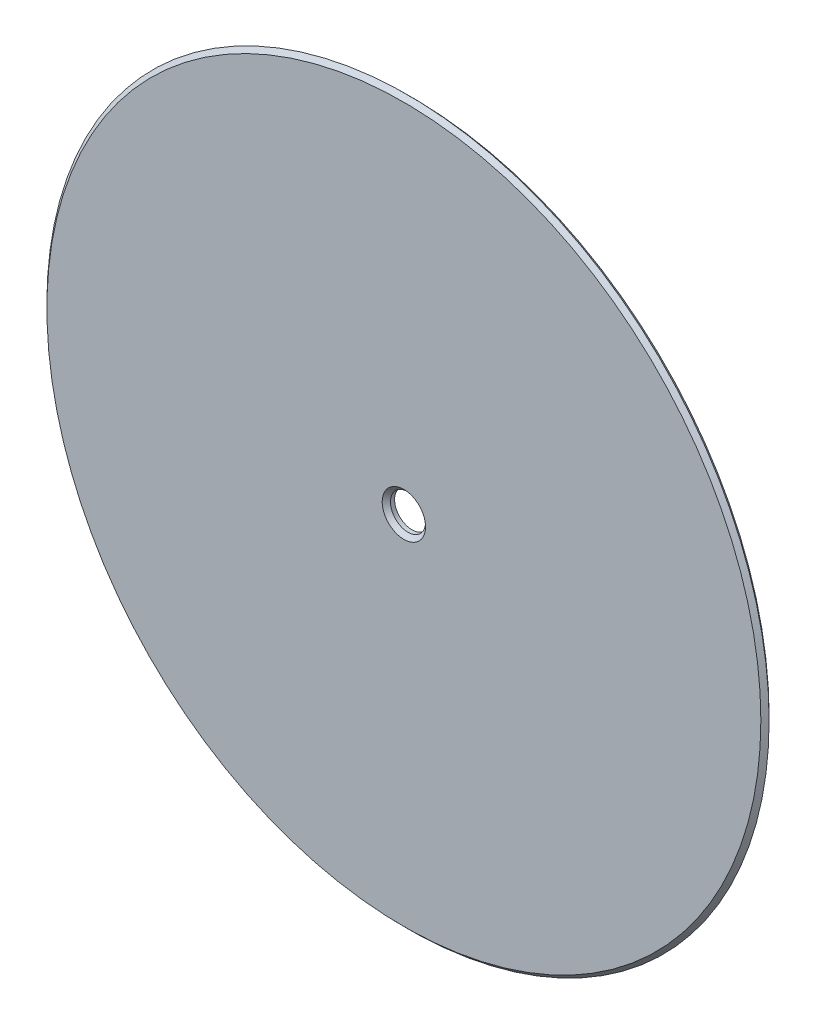
SolidWorks part; units mm, degrees
ref_plane "Front Plane" through (0, 0, 0) normal (0, 0, 1) x (1, 0, 0)
ref_plane "Top Plane" through (0, 0, 0) normal (0, 1, 0) x (1, 0, 0)
ref_plane "Right Plane" through (0, 0, 0) normal (1, 0, 0) x (0, 0, -1)
sketch "Sketch1" plane through (0, 0, 0) normal (0, 0, 1) x (1, 0, 0)
  circle A0 centre (0, 0) radius 44.45
  circle A1 centre (0, 0) radius 2.159
  dimension "D1" = 88.9
  dimension "D2" = 4.318
extrude "Boss-Extrude1" add sketch "Sketch1" along normal blind 1.016
chamfer "Chamfer2" distance 0.508 angle 45 3 edges at (2.159, 0, 1.016) (44.45, 0, 1.016) (44.45, 0, 0)
